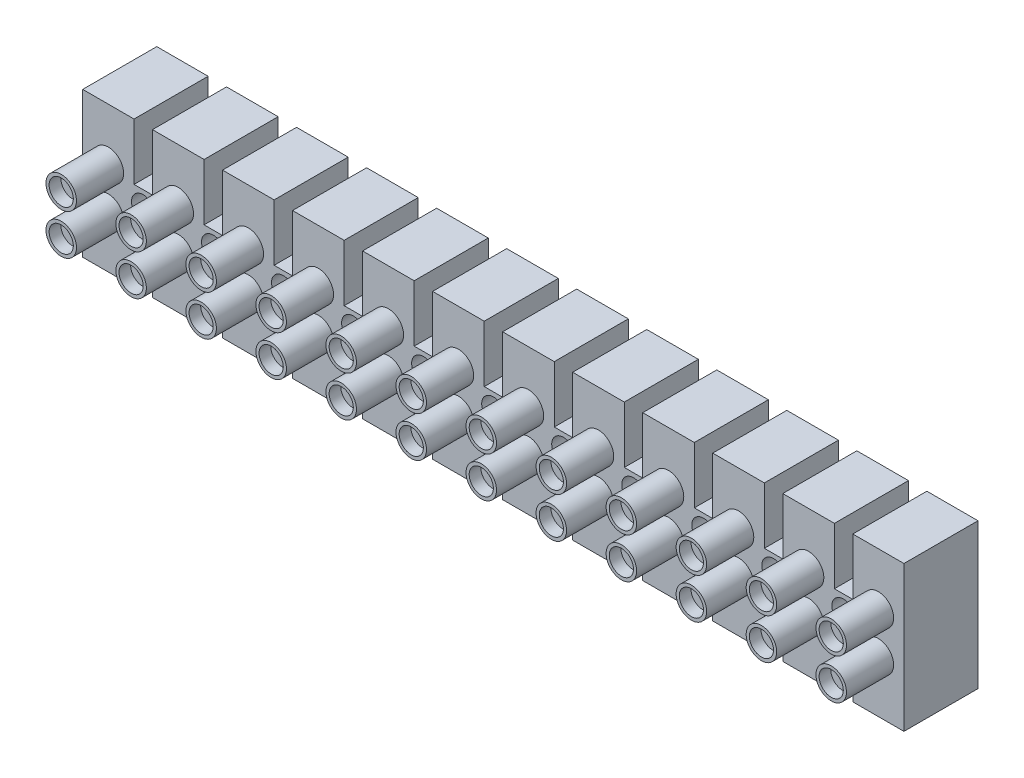
SolidWorks part; units mm, degrees
ref_plane "Front Plane" through (0, 0, 0) normal (0, 0, 1) x (1, 0, 0)
ref_plane "Top Plane" through (0, 0, 0) normal (0, 1, 0) x (1, 0, 0)
ref_plane "Right Plane" through (0, 0, 0) normal (1, 0, 0) x (0, 0, -1)
sketch "Sketch1" plane through (0, 0, 0) normal (0, 0, 1) x (1, 0, 0)
  line L1 (0, 16.9545) -> (95.758, 16.9545)
  line L2 (0, 16.9545) -> (0, 0)
  line L3 (0, 0) -> (95.758, 0)
  line L4 (95.758, 16.9545) -> (95.758, 0)
  dimension "D1" = 95.758
  dimension "D2" = 16.9545
extrude "Boss-Extrude1" add sketch "Sketch1" along normal blind 8.636
sketch "Sketch2" plane through (0, 0, 8.636) normal (0, 0, 1) x (1, 0, 0)
  line L0 (0, 8.4773) -> (95.758, 8.4773) construction
  line L1 (0, 16.9545) -> (0, 0) construction
  line L2 (95.758, 0) -> (95.758, 16.9545) construction
  line L3 (22.3202, 16.9545) -> (24.4666, 16.9545)
  line L4 (5.988, 16.9545) -> (8.1343, 16.9545)
  line L5 (5.988, 16.9545) -> (5.9881, 10.3505)
  line L6 (5.9881, 10.3505) -> (8.1343, 10.3505)
  line L7 (8.1343, 16.9545) -> (8.1343, 10.3505)
  line L8 (14.1542, 16.9545) -> (16.3005, 16.9545)
  line L9 (95.758, 16.9545) -> (0, 16.9545) construction
  line L10 (7.0612, 16.9545) -> (7.0612, 0) construction
  line L11 (15.2273, 16.9545) -> (15.2273, 0) construction
  line L12 (23.3934, 16.9545) -> (23.3934, 0) construction
  line L13 (31.5595, 16.9545) -> (31.5595, 0) construction
  line L14 (39.7256, 16.9545) -> (39.7256, 0) construction
  line L15 (47.8917, 16.9545) -> (47.8917, 0) construction
  line L16 (56.0578, 16.9545) -> (56.0578, 0) construction
  line L17 (64.2239, 16.9545) -> (64.2239, 0) construction
  line L18 (72.39, 16.9545) -> (72.39, 0) construction
  line L19 (88.7222, 16.9545) -> (88.7222, 0) construction
  line L20 (80.5561, 16.9545) -> (80.5561, 0) construction
  line L21 (0, 0) -> (95.758, 0) construction
  line L22 (14.1542, 16.9545) -> (14.1542, 10.3505)
  line L23 (14.1542, 10.3505) -> (16.3005, 10.3505)
  line L24 (16.3005, 16.9545) -> (16.3005, 10.3505)
  line L25 (22.3202, 16.9545) -> (22.3203, 10.3505)
  line L26 (22.3203, 10.3505) -> (24.4666, 10.3505)
  line L27 (24.4666, 16.9545) -> (24.4666, 10.3505)
  line L28 (30.4864, 16.9545) -> (32.6326, 16.9545)
  line L29 (30.4864, 16.9545) -> (30.4864, 10.3505)
  line L30 (30.4864, 10.3505) -> (32.6327, 10.3505)
  line L31 (32.6326, 16.9545) -> (32.6327, 10.3505)
  line L32 (38.6525, 16.9545) -> (40.7988, 16.9545)
  line L33 (38.6525, 16.9545) -> (38.6525, 10.3505)
  line L34 (38.6525, 10.3505) -> (40.7988, 10.3505)
  line L35 (40.7988, 16.9545) -> (40.7988, 10.3505)
  line L36 (46.8186, 16.9545) -> (48.9648, 16.9545)
  line L37 (46.8186, 16.9545) -> (46.8186, 10.3505)
  line L38 (46.8186, 10.3505) -> (48.9649, 10.3505)
  line L39 (48.9648, 16.9545) -> (48.9649, 10.3505)
  line L40 (54.9847, 16.9545) -> (57.131, 16.9545)
  line L41 (54.9847, 16.9545) -> (54.9847, 10.3505)
  line L42 (54.9847, 10.3505) -> (57.131, 10.3505)
  line L43 (57.131, 16.9545) -> (57.131, 10.3505)
  line L44 (63.1508, 16.9545) -> (65.2971, 16.9545)
  line L45 (63.1508, 16.9545) -> (63.1508, 10.3505)
  line L46 (63.1508, 10.3505) -> (65.2971, 10.3505)
  line L47 (65.2971, 16.9545) -> (65.2971, 10.3505)
  line L48 (71.3169, 16.9545) -> (73.4631, 16.9545)
  line L49 (71.3169, 16.9545) -> (71.3169, 10.3505)
  line L50 (71.3169, 10.3505) -> (73.4631, 10.3505)
  line L51 (73.4631, 16.9545) -> (73.4631, 10.3505)
  line L52 (79.483, 16.9545) -> (81.6292, 16.9545)
  line L53 (79.483, 16.9545) -> (79.483, 10.3505)
  line L54 (79.483, 10.3505) -> (81.6293, 10.3505)
  line L55 (81.6292, 16.9545) -> (81.6293, 10.3505)
  line L56 (87.6491, 16.9545) -> (89.7953, 16.9545)
  line L57 (87.6491, 16.9545) -> (87.6491, 10.3505)
  line L58 (87.6491, 10.3505) -> (89.7953, 10.3505)
  line L59 (89.7953, 16.9545) -> (89.7953, 10.3505)
  line L60 (5.988, 6.604) -> (8.1343, 6.604)
  line L61 (5.988, 6.604) -> (5.9881, 0)
  line L62 (5.9881, 0) -> (8.1343, 0)
  line L63 (8.1343, 6.604) -> (8.1343, 0)
  line L64 (14.1542, 6.604) -> (16.3005, 6.604)
  line L65 (14.1542, 6.604) -> (14.1542, 0)
  line L66 (14.1542, 0) -> (16.3005, 0)
  line L67 (16.3005, 6.604) -> (16.3005, 0)
  line L68 (22.3203, 6.604) -> (24.4666, 6.604)
  line L69 (22.3203, 6.604) -> (22.3203, 0)
  line L70 (22.3203, 0) -> (24.4666, 0)
  line L71 (24.4666, 6.604) -> (24.4666, 0)
  line L72 (30.4864, 6.604) -> (32.6326, 6.604)
  line L73 (30.4864, 6.604) -> (30.4864, 0)
  line L74 (30.4864, 0) -> (32.6326, 0)
  line L75 (32.6326, 6.604) -> (32.6326, 0)
  line L76 (38.6525, 6.604) -> (40.7987, 6.604)
  line L77 (38.6525, 6.604) -> (38.6525, 0)
  line L78 (38.6525, 0) -> (40.7987, 0)
  line L79 (40.7987, 6.604) -> (40.7987, 0)
  line L80 (48.9649, 6.604) -> (46.8186, 6.604)
  line L81 (48.9649, 6.604) -> (48.9649, 0)
  line L82 (48.9649, 0) -> (46.8186, 0)
  line L83 (46.8186, 6.604) -> (46.8186, 0)
  line L84 (57.131, 6.604) -> (54.9847, 6.604)
  line L85 (57.131, 6.604) -> (57.131, 0)
  line L86 (57.131, 0) -> (54.9847, 0)
  line L87 (54.9847, 6.604) -> (54.9847, 0)
  line L88 (63.1508, 6.604) -> (65.2971, 6.604)
  line L89 (63.1508, 6.604) -> (63.1508, 0)
  line L90 (63.1508, 0) -> (65.2971, 0)
  line L91 (65.2971, 6.604) -> (65.2971, 0)
  line L92 (71.3169, 6.604) -> (73.4631, 6.604)
  line L93 (71.3169, 6.604) -> (71.3169, 0)
  line L94 (71.3169, 0) -> (73.4632, 0)
  line L95 (73.4631, 6.604) -> (73.4632, 0)
  line L96 (79.483, 6.604) -> (81.6292, 6.604)
  line L97 (79.483, 6.604) -> (79.483, 0)
  line L98 (79.483, 0) -> (81.6293, 0)
  line L99 (81.6292, 6.604) -> (81.6293, 0)
  line L100 (89.7953, 6.604) -> (87.6491, 6.604)
  line L101 (89.7953, 6.604) -> (89.7953, 0)
  line L102 (89.7953, 0) -> (87.6491, 0)
  line L103 (87.6491, 6.604) -> (87.6491, 0)
  circle A0 centre (15.2273, 8.4773) radius 1.3716
  circle A1 centre (23.3934, 8.4773) radius 1.3716
  circle A2 centre (31.5595, 8.4773) radius 1.3716
  circle A3 centre (39.7256, 8.4773) radius 1.3716
  circle A4 centre (47.8917, 8.4773) radius 1.3716
  circle A5 centre (56.0578, 8.4773) radius 1.3716
  circle A6 centre (7.0612, 8.4773) radius 1.3716
  circle A7 centre (64.2239, 8.4773) radius 1.3716
  circle A8 centre (72.39, 8.4773) radius 1.3716
  circle A9 centre (80.5561, 8.4773) radius 1.3716
  circle A10 centre (88.7222, 8.4773) radius 1.3716
  dimension "D1" = 2.7432
  dimension "D2" = 7.0358
  dimension "D3" = 8.1661
  dimension "D4" = 8.1661
  dimension "D5" = 8.1661
  dimension "D6" = 8.1661
  dimension "D7" = 8.1661
  dimension "D8" = 8.1661
  dimension "D9" = 8.1661
  dimension "D10" = 8.1661
  dimension "D11" = 8.1661
  dimension "D12" = 8.1661
  dimension "D13" = 2.1463
  dimension "D14" = 6.604
extrude "Cut-Extrude2" cut sketch "Sketch2" against normal up to surface (8.636 mm away) up to face at (47.879, 8.4773, 0)
sketch "Sketch3" plane through (0, 0, 8.636) normal (0, 0, 1) x (1, 0, 0)
  line L0 (0, 6.1087) -> (95.758, 6.1087) construction
  line L1 (79.483, 16.9545) -> (73.4631, 16.9545) construction
  line L2 (0, 16.9545) -> (0, 0) construction
  line L3 (95.758, 0) -> (95.758, 16.9545) construction
  line L4 (95.758, 10.8458) -> (0, 10.8458) construction
  line L5 (47.879, 10.8458) -> (47.879, 6.1087) construction
  line L6 (95.758, 8.4773) -> (0, 8.4773) construction
  line L7 (92.7767, 16.9545) -> (92.7767, 0) construction
  line L8 (84.6392, 16.9545) -> (84.6392, 0) construction
  line L9 (76.4731, 16.9545) -> (76.4731, 0) construction
  line L10 (68.307, 16.9545) -> (68.307, 0) construction
  line L11 (60.1409, 16.9545) -> (60.1409, 0) construction
  line L12 (51.9748, 16.9545) -> (51.9748, 0) construction
  line L13 (43.8087, 16.9545) -> (43.8087, 0) construction
  line L14 (35.6425, 16.9545) -> (35.6425, 0) construction
  line L15 (27.4765, 16.9545) -> (27.4765, 0) construction
  line L16 (19.3103, 16.9545) -> (19.3104, 0) construction
  line L17 (11.1442, 16.9545) -> (11.1443, 0) construction
  line L18 (2.994, 16.9545) -> (2.994, 0) construction
  line L19 (5.988, 16.9545) -> (0, 16.9545) construction
  line L20 (0, 0) -> (5.9881, 0) construction
  line L21 (14.1542, 16.9545) -> (8.1343, 16.9545) construction
  line L22 (8.1343, 0) -> (14.1542, 0) construction
  line L23 (22.3202, 16.9545) -> (16.3005, 16.9545) construction
  line L24 (16.3005, 0) -> (22.3203, 0) construction
  line L25 (30.4864, 16.9545) -> (24.4666, 16.9545) construction
  line L26 (24.4666, 0) -> (30.4864, 0) construction
  line L27 (38.6525, 16.9545) -> (32.6326, 16.9545) construction
  line L28 (32.6326, 0) -> (38.6525, 0) construction
  line L29 (46.8186, 16.9545) -> (40.7988, 16.9545) construction
  line L30 (40.7987, 0) -> (46.8186, 0) construction
  line L31 (54.9847, 16.9545) -> (48.9648, 16.9545) construction
  line L32 (48.9649, 0) -> (54.9847, 0) construction
  line L33 (63.1508, 16.9545) -> (57.131, 16.9545) construction
  line L34 (57.131, 0) -> (63.1508, 0) construction
  line L35 (71.3169, 16.9545) -> (65.2971, 16.9545) construction
  line L36 (65.2971, 0) -> (71.3169, 0) construction
  line L37 (73.4632, 0) -> (79.483, 0) construction
  line L38 (87.6491, 16.9545) -> (81.6292, 16.9545) construction
  line L39 (81.6293, 0) -> (87.6491, 0) construction
  line L40 (95.758, 16.9545) -> (89.7953, 16.9545) construction
  line L41 (89.7953, 0) -> (95.758, 0) construction
  circle A0 centre (92.7767, 6.1087) radius 1.778
  circle A1 centre (11.1443, 10.8458) radius 1.778
  circle A2 centre (19.3103, 10.8458) radius 1.778
  circle A3 centre (27.4765, 10.8458) radius 1.778
  circle A4 centre (35.6425, 10.8458) radius 1.778
  circle A5 centre (43.8087, 10.8458) radius 1.778
  circle A6 centre (51.9748, 10.8458) radius 1.778
  circle A7 centre (60.1409, 10.8458) radius 1.778
  circle A8 centre (68.307, 10.8458) radius 1.778
  circle A9 centre (76.4731, 10.8458) radius 1.778
  circle A10 centre (84.6392, 10.8458) radius 1.778
  circle A11 centre (92.7767, 10.8458) radius 1.778
  circle A12 centre (2.994, 10.8458) radius 1.778
  circle A13 centre (2.994, 6.1087) radius 1.778
  circle A14 centre (11.1443, 6.1087) radius 1.778
  circle A15 centre (19.3103, 6.1087) radius 1.778
  circle A16 centre (27.4765, 6.1087) radius 1.778
  circle A17 centre (35.6426, 6.1087) radius 1.778
  circle A18 centre (43.8087, 6.1087) radius 1.778
  circle A19 centre (51.9748, 6.1087) radius 1.778
  circle A20 centre (60.1409, 6.1087) radius 1.778
  circle A21 centre (68.307, 6.1087) radius 1.778
  circle A22 centre (76.4731, 6.1087) radius 1.778
  circle A23 centre (84.6392, 6.1087) radius 1.778
  point P16 (47.879, 8.4773)
  dimension "D1" = 3.556
  dimension "D2" = 4.7371
extrude "Boss-Extrude2" add sketch "Sketch3" along normal blind 5.4991
sketch "Sketch4" plane through (0, 0, 14.1351) normal (0, 0, 1) x (1, 0, 0)
  circle A0 centre (11.1443, 6.1087) radius 1.4097
  circle A1 centre (19.3103, 6.1087) radius 1.4097
  circle A2 centre (27.4765, 6.1087) radius 1.4097
  circle A3 centre (35.6426, 6.1087) radius 1.4097
  circle A4 centre (43.8087, 6.1087) radius 1.4097
  circle A5 centre (51.9748, 6.1087) radius 1.4097
  circle A6 centre (60.1409, 6.1087) radius 1.4097
  circle A7 centre (68.307, 6.1087) radius 1.4097
  circle A8 centre (76.4731, 6.1087) radius 1.4097
  circle A9 centre (84.6392, 6.1087) radius 1.4097
  circle A10 centre (92.7767, 6.1087) radius 1.4097
  circle A11 centre (92.7767, 10.8458) radius 1.4097
  circle A12 centre (84.6392, 10.8458) radius 1.4097
  circle A13 centre (76.4731, 10.8458) radius 1.4097
  circle A14 centre (68.307, 10.8458) radius 1.4097
  circle A15 centre (60.1409, 10.8458) radius 1.4097
  circle A16 centre (51.9748, 10.8458) radius 1.4097
  circle A17 centre (43.8087, 10.8458) radius 1.4097
  circle A18 centre (35.6425, 10.8458) radius 1.4097
  circle A19 centre (27.4765, 10.8458) radius 1.4097
  circle A20 centre (19.3103, 10.8458) radius 1.4097
  circle A21 centre (11.1443, 10.8458) radius 1.4097
  circle A22 centre (2.994, 10.8458) radius 1.4097
  circle A23 centre (2.994, 6.1087) radius 1.4097
  circle A26 centre (92.7767, 10.8458) radius 1.778 construction
  circle A27 centre (84.6392, 10.8458) radius 1.778 construction
  circle A28 centre (76.4731, 10.8458) radius 1.778 construction
  circle A29 centre (68.307, 10.8458) radius 1.778 construction
  circle A30 centre (60.1409, 10.8458) radius 1.778 construction
  circle A31 centre (51.9748, 10.8458) radius 1.778 construction
  circle A32 centre (43.8087, 10.8458) radius 1.778 construction
  circle A33 centre (35.6425, 10.8458) radius 1.778 construction
  circle A34 centre (27.4765, 10.8458) radius 1.778 construction
  circle A35 centre (19.3103, 10.8458) radius 1.778 construction
  circle A36 centre (11.1443, 10.8458) radius 1.778 construction
  circle A37 centre (2.994, 10.8458) radius 1.778 construction
  circle A38 centre (2.994, 6.1087) radius 1.778 construction
  circle A39 centre (11.1443, 6.1087) radius 1.778 construction
  circle A40 centre (19.3103, 6.1087) radius 1.778 construction
  circle A41 centre (27.4765, 6.1087) radius 1.778 construction
  circle A42 centre (35.6426, 6.1087) radius 1.778 construction
  circle A43 centre (43.8087, 6.1087) radius 1.778 construction
  circle A44 centre (51.9748, 6.1087) radius 1.778 construction
  circle A45 centre (60.1409, 6.1087) radius 1.778 construction
  circle A46 centre (68.307, 6.1087) radius 1.778 construction
  circle A47 centre (76.4731, 6.1087) radius 1.778 construction
  circle A48 centre (84.6392, 6.1087) radius 1.778 construction
  circle A49 centre (92.7767, 6.1087) radius 1.778 construction
  dimension "D1" = 2.8194
extrude "Cut-Extrude3" cut sketch "Sketch4" against normal blind 1.3589
